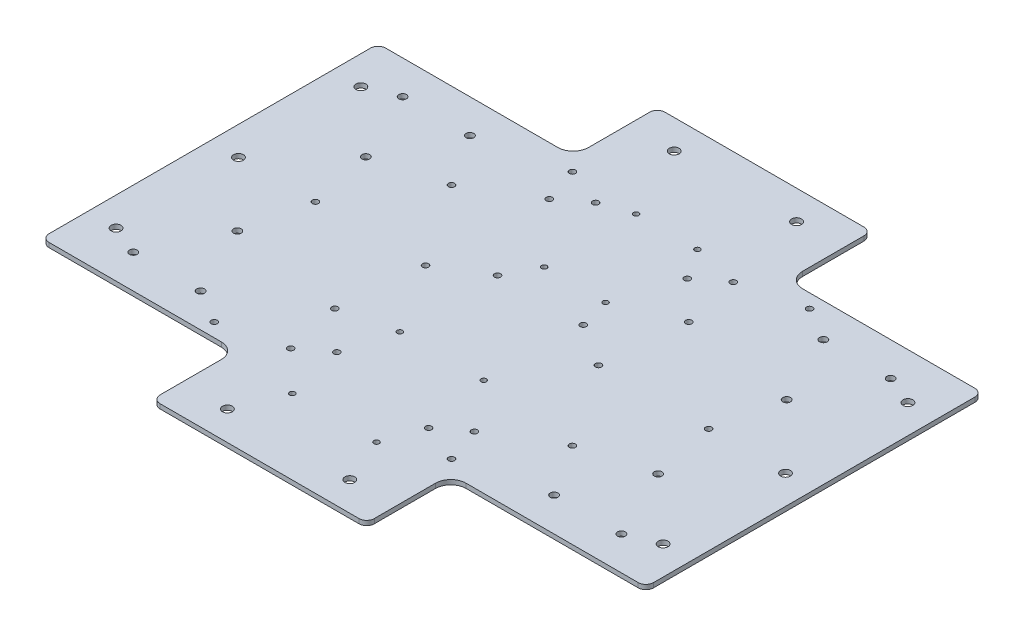
SolidWorks part; units mm, degrees
material "1060 Сплав"
ref_plane "Спереди" through (0, 0, 0) normal (0, 0, 1) x (1, 0, 0)
ref_plane "Сверху" through (0, 0, 0) normal (0, 1, 0) x (1, 0, 0)
ref_plane "Справа" through (0, 0, 0) normal (1, 0, 0) x (0, 0, -1)
sketch "Эскиз1" plane through (0, 0, 0) normal (0, 1, 0) x (1, 0, 0)
  line L1 (-65, -165) -> (65, -165)
  line L2 (-197.5, -105) -> (-197.5, 105)
  line L3 (-65, 165) -> (65, 165)
  line L4 (197.5, -105) -> (197.5, 105)
  line L5 (197.5, -105) -> (137.5, -105) construction
  line L6 (137.5, -110) -> (137.5, -66.2968) construction
  line L18 (-284.5497, 0) -> (284.3305, 0) construction
  line L19 (-160.9018, 110) -> (-134.9018, 110)
  line L39 (-70, 120) -> (-70, 160)
  line L40 (0, 262.7398) -> (0, -186.5795) construction
  line L41 (-192.5, 110) -> (-80, 110)
  line L43 (-192.5, -110) -> (-80, -110)
  line L44 (-70, -120) -> (-70, -160)
  line L45 (70, 120) -> (70, 160)
  line L46 (192.5, 110) -> (80, 110)
  line L47 (192.5, -110) -> (80, -110)
  line L48 (70, -120) -> (70, -160)
  line L54 (160.9018, -110) -> (134.9018, -110)
  line L60 (160.9018, 110) -> (134.9018, 110)
  line L65 (40, -146) -> (-40, -146) construction
  line L66 (-178.7687, -80) -> (-178.7687, 80) construction
  arc A0 (70, -120) -> (80, -110) centre (80, -120) cw
  arc A1 (70, 120) -> (80, 110) centre (80, 120) ccw
  arc A2 (-80, -110) -> (-70, -120) centre (-80, -120) cw
  arc A3 (-70, 120) -> (-80, 110) centre (-80, 120) cw
  arc A4 (192.5, -110) -> (197.5, -105) centre (192.5, -105) ccw
  arc A5 (70, -160) -> (65, -165) centre (65, -160) cw
  arc A6 (-70, -160) -> (-65, -165) centre (-65, -160) ccw
  arc A7 (-192.5, -110) -> (-197.5, -105) centre (-192.5, -105) cw
  arc A8 (-192.5, 110) -> (-197.5, 105) centre (-192.5, 105) ccw
  arc A9 (197.5, 105) -> (192.5, 110) centre (192.5, 105) ccw
  arc A10 (70, 160) -> (65, 165) centre (65, 160) ccw
  arc A11 (-70, 160) -> (-65, 165) centre (-65, 160) cw
  circle A12 centre (40, 146) radius 3.2
  circle A13 centre (40, -146) radius 3.2
  circle A14 centre (-40, -146) radius 3.2
  circle A15 centre (-40, 146) radius 3.2
  circle A16 centre (-178.7687, 80) radius 3.2
  circle A17 centre (-178.7687, -80) radius 3.2
  circle A18 centre (-178.7687, 0) radius 3.2
  circle A19 centre (178.7687, 80) radius 3.2
  circle A20 centre (178.7687, 0) radius 3.2
  circle A21 centre (178.7687, -80) radius 3.2
  circle A22 centre (137.5, -42) radius 2.5
  circle A23 centre (159.5, -88) radius 2.5
  circle A24 centre (115.5, -88) radius 2.5
  circle A25 centre (-159.5, -88) radius 2.5
  circle A26 centre (-137.5, -42) radius 2.5
  circle A27 centre (-115.5, -88) radius 2.5
  circle A28 centre (159.5, 88) radius 2.5
  circle A29 centre (137.5, 42) radius 2.5
  circle A30 centre (115.5, 88) radius 2.5
  circle A31 centre (-115.5, 88) radius 2.5
  circle A32 centre (-137.5, 42) radius 2.5
  circle A33 centre (-159.5, 88) radius 2.5
  point P0 (0, 0)
  point P3 (70, -110)
  point P17 (-147.9018, 110)
  point P18 (-147.9018, 110)
  point P46 (70, 110)
  point P52 (-70, -110)
  point P55 (-70, 110)
  point P56 (-147.9018, 0)
  point P59 (-178.7687, 0)
  point P62 (178.7687, 80)
  point P77 (197.5, -110)
  point P80 (70, -165)
  point P83 (-70, -165)
  point P86 (-197.5, -110)
  point P89 (-197.5, 110)
  point P92 (197.5, 110)
  point P95 (70, 165)
  point P98 (-70, 165)
  point P99 (178.7687, 0)
  point P100 (40, 146)
  point P101 (178.7687, -80)
  point P103 (-40, 146)
  dimension "D2" = 19
  dimension "D6" = 10
  dimension "D11" = 40
  dimension "D12" = 40
  dimension "D4" = 5
  dimension "D17" = 5
  dimension "D9" = 6.4
  dimension "D3" = 38
  dimension "D14" = 5
  dimension "D5" = 330
  dimension "D7" = 395
  dimension "D8" = 68
  dimension "D10" = 60
  dimension "D13" = 22
  dimension "D15" = 80
  dimension "D16" = 80
  dimension "D18" = 18.7313
  dimension "D19" = 19
  dimension "D20" = 140
extrude "Бобышка-Вытянуть1" add sketch "Эскиз1" along normal blind 3 separate body contours A11 L39 A3 L41 L43 A2 L44 A6 L1 A5 L48 A0 L47 L46 A1 L45 A10 L3 | L4 A9 L46 L47 A4 | L46 | L47 | L41 A8 L2 A7 L43 | L19 region at (0, 0, 0)
sketch "Эскиз2" plane through (0, 3, 0) normal (0, 1, 0) x (1, 0, 0)
  line L0 (197.5, 0) -> (-197.5, 0) construction
  line L1 (197.5, -105) -> (197.5, 105) construction
  line L2 (-197.5, -105) -> (-197.5, 105) construction
  line L3 (0, 165) -> (0, -165) construction
  line L4 (-65, 165) -> (65, 165) construction
  line L5 (-65, -165) -> (65, -165) construction
  line L6 (192.5, 110) -> (80, 110) construction
  circle A0 centre (128.5, 0) radius 2
  circle A1 centre (56.5, 0) radius 2
  circle A2 centre (93.5, 101) radius 2
  circle A3 centre (61.5, 54) radius 2
  circle A4 centre (49.5, 74) radius 2 construction
  circle A5 centre (53.5, 91.0922) radius 2
  circle A6 centre (36.503, 78.0468) radius 2
  circle A7 centre (28.6809, 17.8719) radius 2
  circle A8 centre (-27.3191, 17.8719) radius 2
  circle A9 centre (27.4963, -46.0223) radius 1.75
  circle A10 centre (93.5, -54.0533) radius 2
  circle A11 centre (61.5, -101.043) radius 2
  circle A12 centre (53.5, -78.0725) radius 2
  circle A13 centre (36.503, -90.9991) radius 2
  circle A14 centre (27.4963, -116.0332) radius 1.75
  circle A15 centre (-27.5526, -116.0332) radius 1.75
  circle A16 centre (-27.3191, -46) radius 1.75
  circle A17 centre (-53.6363, -90.9991) radius 2
  circle A18 centre (-36.4017, -78.0725) radius 2
  circle A19 centre (-93.5268, -101.043) radius 2
  circle A20 centre (-61.7277, -54.0533) radius 2
  circle A21 centre (-36.4017, 91.0922) radius 2
  circle A22 centre (-53.6363, 78.0468) radius 2
  circle A23 centre (-61.5417, 101) radius 2
  circle A24 centre (-93.5268, 54) radius 2
  circle A25 centre (-128.5, 0) radius 2
  circle A26 centre (-56.5, 0) radius 2
  circle A27 centre (-16.8323, 37.8725) radius 1.75
  circle A28 centre (-16.7978, 97.9276) radius 1.75
  circle A29 centre (23.276, 97.9276) radius 1.75
  circle A30 centre (23.276, 37.8725) radius 1.75
  point P15 (97.5, 105)
  point P19 (57.5, 50)
  point P24 (53.5, 101)
  point P25 (52.5, 81)
  dimension "D1" = 69
  dimension "D2" = 4
  dimension "D6" = 4
  dimension "D11" = 4
  dimension "D16" = 4
  dimension "D4" = 100
  dimension "D5" = 5
  dimension "D7" = 4
  dimension "D8" = 4
  dimension "D9" = 51
  dimension "D10" = 36
  dimension "D12" = 4
  dimension "D13" = 4
  dimension "D14" = 31
  dimension "D15" = 1
  dimension "D17" = 7
  dimension "D18" = 3
  dimension "D3" = 2
extrude "Вырез-Вытянуть1" cut sketch "Эскиз2" against normal blind 10
